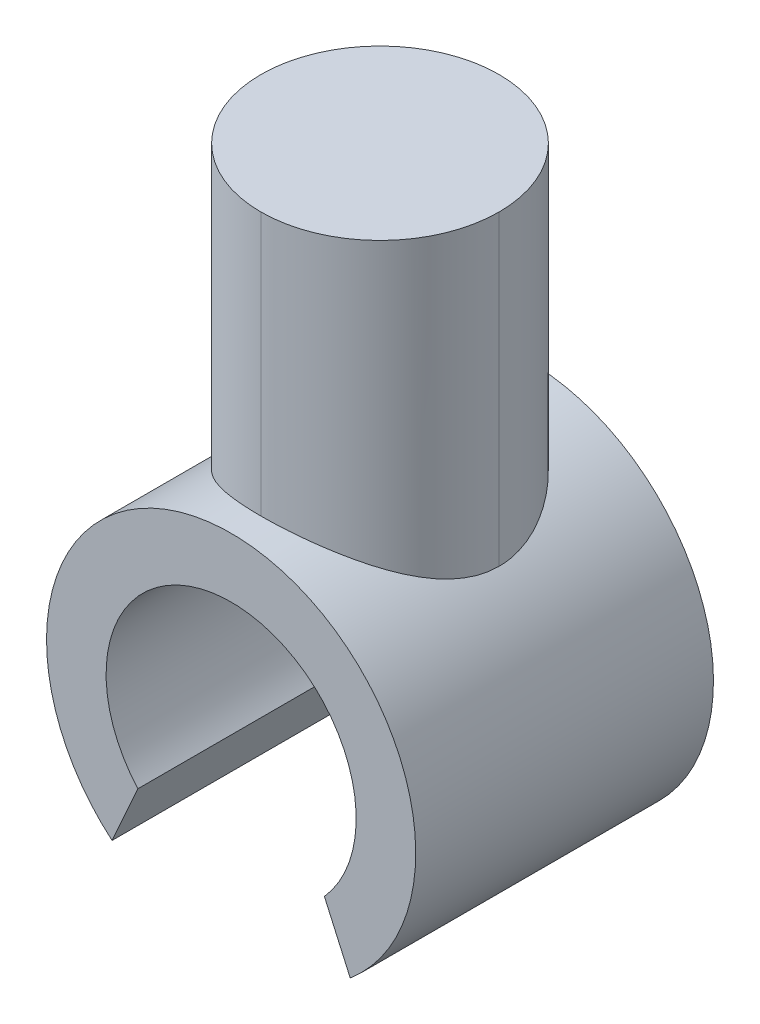
SolidWorks part; units mm, degrees
ref_plane "Front Plane" through (0, 0, 0) normal (0, 0, 1) x (1, 0, 0)
ref_plane "Top Plane" through (0, 0, 0) normal (0, 1, 0) x (1, 0, 0)
ref_plane "Right Plane" through (0, 0, 0) normal (1, 0, 0) x (0, 0, -1)
sketch "Sketch1" plane through (0, 0, 0) normal (0, 0, 1) x (1, 0, 0)
  line L1 (-50.8, 112.3216) -> (-50.8, -18.579)
  line L2 (50.8, 112.3216) -> (50.8, -18.579)
  line L5 (0, 112.3216) -> (-50.8, 112.3216)
  line L7 (0, 112.3216) -> (50.8, 112.3216)
  line L12 (-50.8, -138.901) -> (-39.7786, -114.2762)
  line L13 (50.8, -138.901) -> (39.7786, -114.2762)
  arc A3 (-50.8, -18.579) -> (-50.8, -138.901) centre (0, -78.74) ccw
  arc A4 (50.8, -18.579) -> (50.8, -138.901) centre (0, -78.74) cw
  arc A5 (39.7786, -114.2762) -> (-39.7786, -114.2762) centre (0, -78.74) ccw
  dimension "D1" = 78.74
  dimension "D7" = 50.8
  dimension "D8" = 50.8
extrude "Boss-Extrude1" add sketch "Sketch1" along normal blind 101.6
sketch "Sketch2" plane through (0, 0, 101.6) normal (0, 0, 1) x (1, 0, 0)
  line L0 (-50.8, -138.901) -> (-39.7786, -114.2762)
  line L1 (50.8, -138.901) -> (39.7786, -114.2762)
  arc A0 (-50.8, -138.901) -> (50.8, -138.901) centre (0, -78.74) cw
  arc A1 (50.8, -138.901) -> (50.8, -18.579) centre (0, -78.74) ccw construction
  arc A2 (-39.7786, -114.2762) -> (39.7786, -114.2762) centre (0, -78.74) cw
  arc A3 (39.7786, -114.2762) -> (-39.7786, -114.2762) centre (0, -78.74) ccw construction
  arc M3 (-50.8, -18.579) -> (-50.8, -138.901) centre (0, -78.74) ccw
  line M4 (-50.8, -138.901) -> (-39.7786, -114.2762)
  arc M5 (-39.7786, -114.2762) -> (39.7786, -114.2762) centre (0, -78.74) cw
  line M6 (39.7786, -114.2762) -> (50.8, -138.901)
  arc M7 (50.8, -138.901) -> (50.8, -18.579) centre (0, -78.74) ccw
extrude "Boss-Extrude3" add sketch "Sketch2" along normal blind 12.7 contours A0 M3 M4 M5 M6 M7 region at (-76.6402, -78.74, 101.6)
sketch "Sketch4" plane through (0, 0, 0) normal (0, 0, -1) x (-1, 0, 0)
  line L0 (50.8, -138.901) -> (39.7786, -114.2762) construction
  line L1 (50.8, -138.901) -> (39.7786, -114.2762)
  line L2 (-50.8, -138.901) -> (-39.7786, -114.2762)
  arc A0 (-50.8, -138.901) -> (50.8, -138.901) centre (0, -78.74) cw
  arc A1 (-39.7786, -114.2762) -> (39.7786, -114.2762) centre (0, -78.74) cw
  arc M3 (-50.8, -18.579) -> (-50.8, -138.901) centre (0, -78.74) ccw
  line M4 (-50.8, -138.901) -> (-39.7786, -114.2762)
  arc M5 (-39.7786, -114.2762) -> (39.7786, -114.2762) centre (0, -78.74) cw
  line M6 (39.7786, -114.2762) -> (50.8, -138.901)
  arc M7 (50.8, -138.901) -> (50.8, -18.579) centre (0, -78.74) ccw
extrude "Boss-Extrude4" add sketch "Sketch4" along normal blind 12.7 contours A0 M3 M4 M5 M6 M7 region at (-47.2059, -125.7308, 0)
fillet "Fillet1" radius 50.8 4 edges at (50.8, 46.8713, 101.6) (50.8, 46.8713, 0) (-50.8, 46.8713, 101.6) (-50.8, 46.8713, 0)
